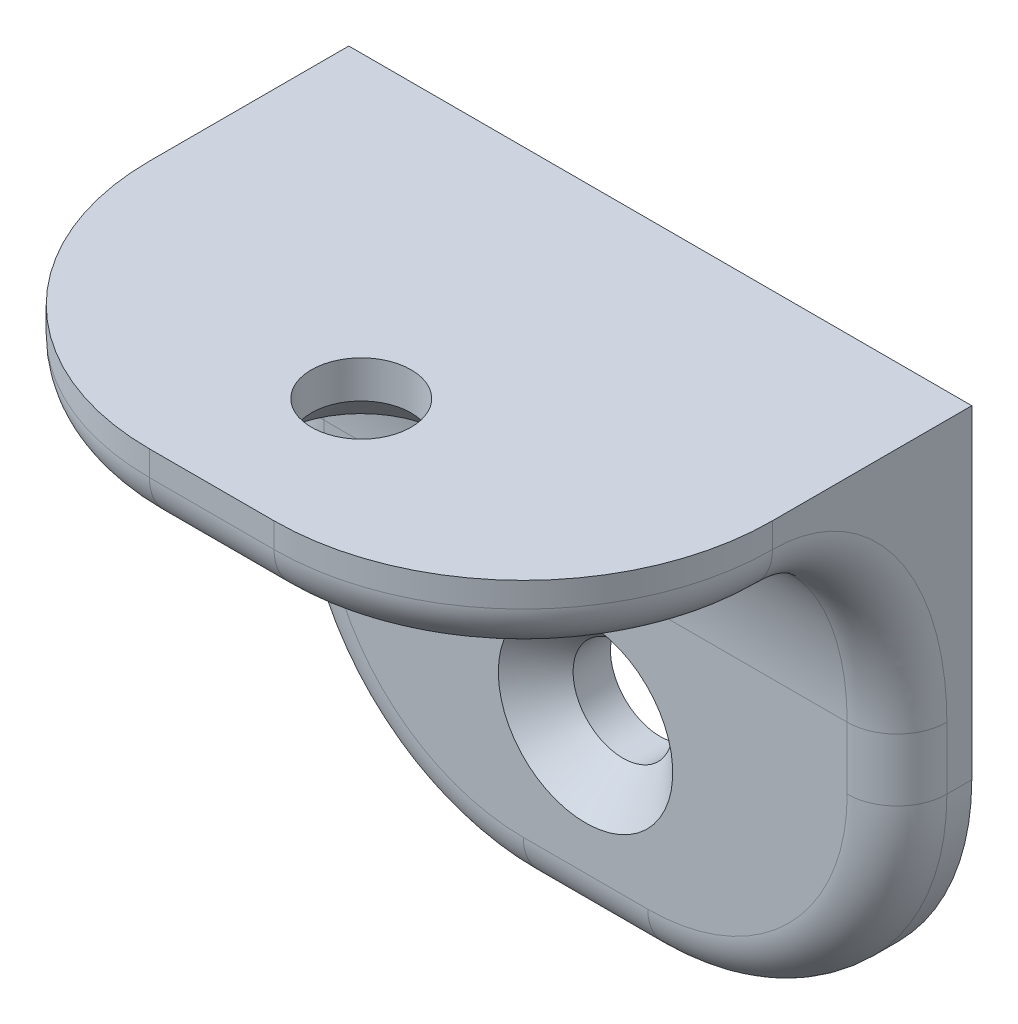
SolidWorks part; units mm, degrees
ref_plane "Front" through (0, 0, 0) normal (0, 0, 1) x (1, 0, 0)
ref_plane "Top" through (0, 0, 0) normal (0, 1, 0) x (1, 0, 0)
ref_plane "Right" through (0, 0, 0) normal (1, 0, 0) x (0, 0, -1)
sketch "Sketch1" plane through (0, 0, 0) normal (1, 0, 0) x (0, 0, -1)
  line L0 (0, 0) -> (0, 25.4)
  line L1 (0, 25.4) -> (-19.05, 25.4)
  line L2 (-19.05, 25.4) -> (-19.05, 29.21)
  line L3 (-19.05, 29.21) -> (3.81, 29.21)
  line L4 (3.81, 29.21) -> (3.81, 0)
  line L5 (3.81, 0) -> (0, 0)
  dimension "D1" = 3.81
  dimension "D2" = 25.4
  dimension "D3" = 19.05
extrude "Boss-Extrude1" add sketch "Sketch1" along normal blind 31.75
fillet "Fillet3" radius 12.7 4 edges at (31.75, 27.305, 19.05) (0, 27.305, 19.05) (31.75, 0, -1.905) (0, 0, -1.905)
fillet "Fillet1" radius 6.35 1 edges at (15.875, 25.4, 0) second distance 9.525 first distance on face at (15.875, 25.4, 9.3434)
fillet "Fillet2" radius 2.54 10 edges at (15.875, 0, 0) (15.875, 25.4, 19.05) (28.0303, 3.7197, 0) (3.7197, 3.7197, 0)
sketch "Sketch3" plane through (0, 0, 0) normal (0, 0, 1) x (1, 0, 0)
  line L0 (0, 9.2075) -> (15.875, 9.2075) construction
  line L1 (0, 15.875) -> (0, 2.54) construction
  line L2 (15.875, 9.2075) -> (15.875, 2.54) construction
  line L3 (12.7, 2.54) -> (19.05, 2.54) construction
  circle A0 centre (15.875, 9.2075) radius 2.54
  dimension "D1" = 5.08
extrude "Cut-Extrude1" cut sketch "Sketch3" against normal through all
sketch "Sketch4" plane through (0, 25.4, 0) normal (0, -1, 0) x (1, 0, 0)
  line L0 (15.875, 11.43) -> (15.875, 16.51) construction
  line L1 (19.05, 16.51) -> (12.7, 16.51) construction
  line L2 (15.875, 11.43) -> (0, 11.43) construction
  line L3 (0, 16.51) -> (0, 6.35) construction
  circle A0 centre (15.875, 11.43) radius 2.54
  dimension "D1" = 5.08
extrude "Cut-Extrude2" cut sketch "Sketch4" against normal through all
chamfer "Chamfer1" distance 1.905 angle 45 2 edges at (18.415, 9.2075, 0) (15.875, 25.4, 8.89)
